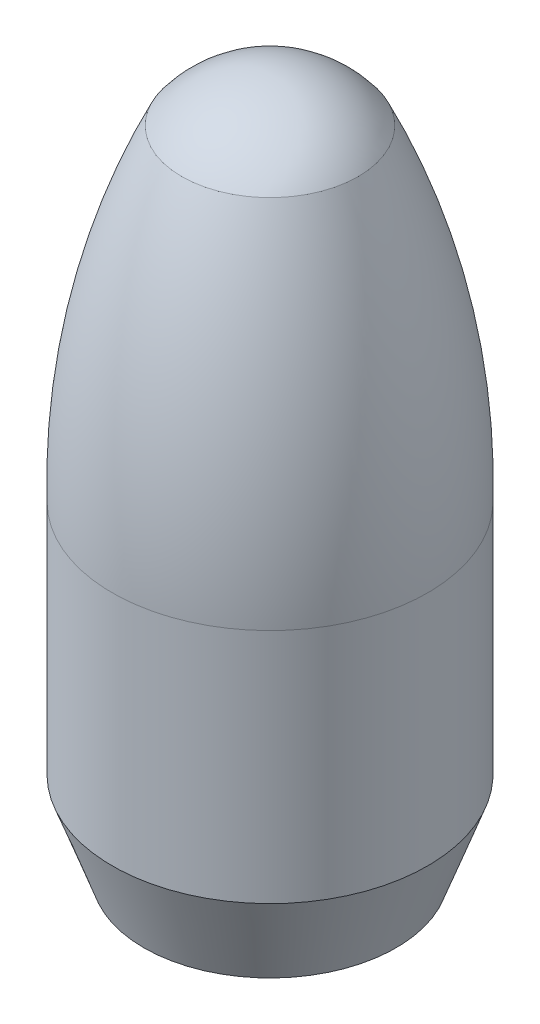
SolidWorks part; units mm, degrees
ref_plane "Front Plane" through (0, 0, 0) normal (0, 0, 1) x (1, 0, 0)
ref_plane "Top Plane" through (0, 0, 0) normal (0, 1, 0) x (1, 0, 0)
ref_plane "Right Plane" through (0, 0, 0) normal (1, 0, 0) x (0, 0, -1)
sketch "Sketch1" plane through (0, 0, 0) normal (0, 0, 1) x (1, 0, 0)
  line L0 (0, -273.8313) -> (0, 273.8313) construction
  line L1 (140, 287) -> (140, 77)
  line L2 (0, 0) -> (112, 0)
  line L3 (112, 0) -> (140, 77)
  line L4 (0, 630) -> (369.8972, 630) construction
  line L5 (0, 576.4501) -> (78.4, 576.4501)
  line L6 (0, 0) -> (0, 576.4501)
  arc A0 (78.4, 576.4501) -> (140, 287) centre (-497.3928, 302.6316) cw
  point P4 (0, 0)
  dimension "D1" = 210
  dimension "D2" = 630
  dimension "D3" = 140
  dimension "D4" = 112
  dimension "D5" = 77
  dimension "D6" = 78.4
revolve "Revolve1" add sketch "Sketch1" angle 360 about L6
dome "Dome1" faces to dome 1 distance 39.2 reverse direction no elliptical dome no face at (0, 576.4501, -78.4) parameters "D1"=39.2
